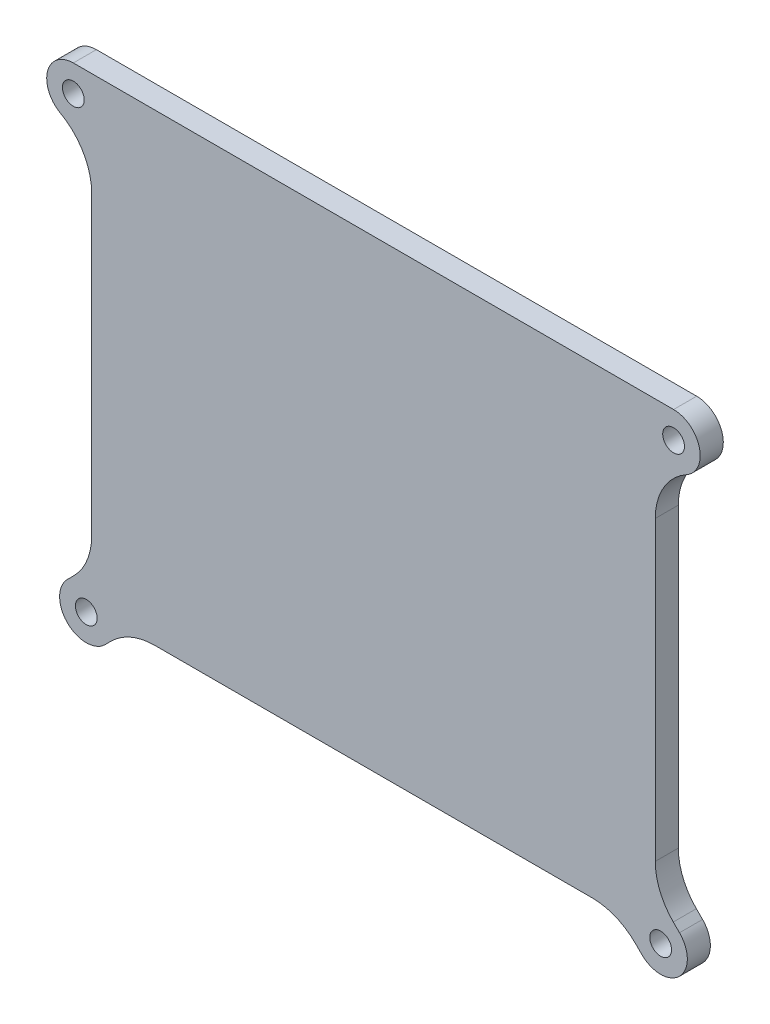
SolidWorks part; units mm, degrees
material "Acrylic (Medium-high impact)"
ref_plane "X-Y Datum" through (0, 0, 0) normal (0, 0, 1) x (1, 0, 0)
ref_plane "X-Z Datum" through (0, 0, 0) normal (0, 1, 0) x (1, 0, 0)
ref_plane "Y-Z Datum" through (0, 0, 0) normal (1, 0, 0) x (0, 0, -1)
sketch "Sketch2" plane through (0, 0, 0) normal (0, 0, 1) x (1, 0, 0)
  line L9 (-58.1813, 26.4968) -> (-58.1812, -34.8238)
  line L10 (-61.901, -43.8041) -> (-63.1828, -45.0859)
  line L11 (-55.4046, -52.8641) -> (-54.1228, -51.5822)
  line L12 (-45.1426, -47.8625) -> (45.1426, -47.8625)
  line L13 (54.1228, -51.5822) -> (55.4046, -52.8641)
  line L14 (63.1828, -45.0859) -> (61.901, -43.8041)
  line L15 (58.1813, -34.8238) -> (58.1812, 26.4968)
  line L24 (61.9639, 47.8625) -> (-61.9639, 47.8625)
  line L25 (-58.1813, 26.4968) -> (-58.1812, -34.8238)
  line L26 (-61.901, -43.8041) -> (-63.1828, -45.0859)
  line L27 (-55.4046, -52.8641) -> (-54.1228, -51.5822)
  line L28 (-45.1426, -47.8625) -> (45.1426, -47.8625)
  line L29 (54.1228, -51.5822) -> (55.4046, -52.8641)
  line L30 (63.1828, -45.0859) -> (61.901, -43.8041)
  line L31 (58.1813, -34.8238) -> (58.1812, 26.4968)
  line L32 (61.9639, 47.8625) -> (-61.9639, 47.8625)
  arc A30 (-61.9639, 47.8625) -> (-64.6587, 37.5679) centre (-61.9639, 42.3625) ccw
  arc A31 (-58.1813, 26.4968) -> (-64.6587, 37.5679) centre (-70.8813, 26.4968) ccw
  arc A32 (-61.901, -43.8041) -> (-58.1812, -34.8238) centre (-70.8812, -34.8238) ccw
  arc A33 (-63.1828, -45.0859) -> (-55.4046, -52.8641) centre (-59.2937, -48.975) ccw
  arc A34 (-45.1426, -47.8625) -> (-54.1228, -51.5822) centre (-45.1426, -60.5625) ccw
  arc A35 (54.1228, -51.5822) -> (45.1426, -47.8625) centre (45.1426, -60.5625) ccw
  arc A36 (55.4046, -52.8641) -> (63.1828, -45.0859) centre (59.2937, -48.975) ccw
  arc A37 (58.1813, -34.8238) -> (61.901, -43.8041) centre (70.8813, -34.8238) ccw
  arc A38 (64.6587, 37.5679) -> (58.1812, 26.4968) centre (70.8812, 26.4968) ccw
  arc A39 (64.6587, 37.5679) -> (61.9639, 47.8625) centre (61.9639, 42.3625) ccw
  arc A40 (-61.9639, 47.8625) -> (-64.6587, 37.5679) centre (-61.9639, 42.3625) ccw
  arc A41 (-58.1813, 26.4968) -> (-64.6587, 37.5679) centre (-70.8813, 26.4968) ccw
  arc A42 (-61.901, -43.8041) -> (-58.1812, -34.8238) centre (-70.8812, -34.8238) ccw
  arc A43 (-63.1828, -45.0859) -> (-55.4046, -52.8641) centre (-59.2937, -48.975) ccw
  arc A44 (-45.1426, -47.8625) -> (-54.1228, -51.5822) centre (-45.1426, -60.5625) ccw
  arc A45 (54.1228, -51.5822) -> (45.1426, -47.8625) centre (45.1426, -60.5625) ccw
  arc A46 (55.4046, -52.8641) -> (63.1828, -45.0859) centre (59.2937, -48.975) ccw
  arc A47 (58.1813, -34.8238) -> (61.901, -43.8041) centre (70.8813, -34.8238) ccw
  arc A48 (64.6587, 37.5679) -> (58.1812, 26.4968) centre (70.8812, 26.4968) ccw
  arc A49 (64.6587, 37.5679) -> (61.9639, 47.8625) centre (61.9639, 42.3625) ccw
  dimension "D1" = 0
extrude "Boss-Extrude1" add sketch "Sketch2" along normal blind 4.7625
hole_wizard "M4 Clearance Hole1" positions "Sketch9" profile "Sketch10" hole size "M4" standard "ANSI Metric" end condition through all
sketch "Sketch9" plane through (0, 0, 4.7625) normal (0, 0, 1) x (1, 0, 0)
  point P17 (-61.9639, 42.3625)
  point P20 (-59.2937, -48.975)
  point P23 (59.2937, -48.975)
  point P26 (61.9639, 42.3625)
sketch "Sketch10" plane through (-61.9639, 42.3625, 4.7625) normal (1, 0, 0) x (0, -1, 0)
  line L0 (0, 0) -> (0, 4.7625)
  line L1 (0, 4.7625) -> (2.25, 4.7625)
  line L2 (2.25, 4.7625) -> (2.25, 0)
  line L5 (2.25, 0) -> (0, 0)
  line L11 (0, -6.35) -> (0, 107.95) construction
  dimension "Thru Hole Dia." = 4.5
  dimension "Thru Hole Depth" = 4.7625
